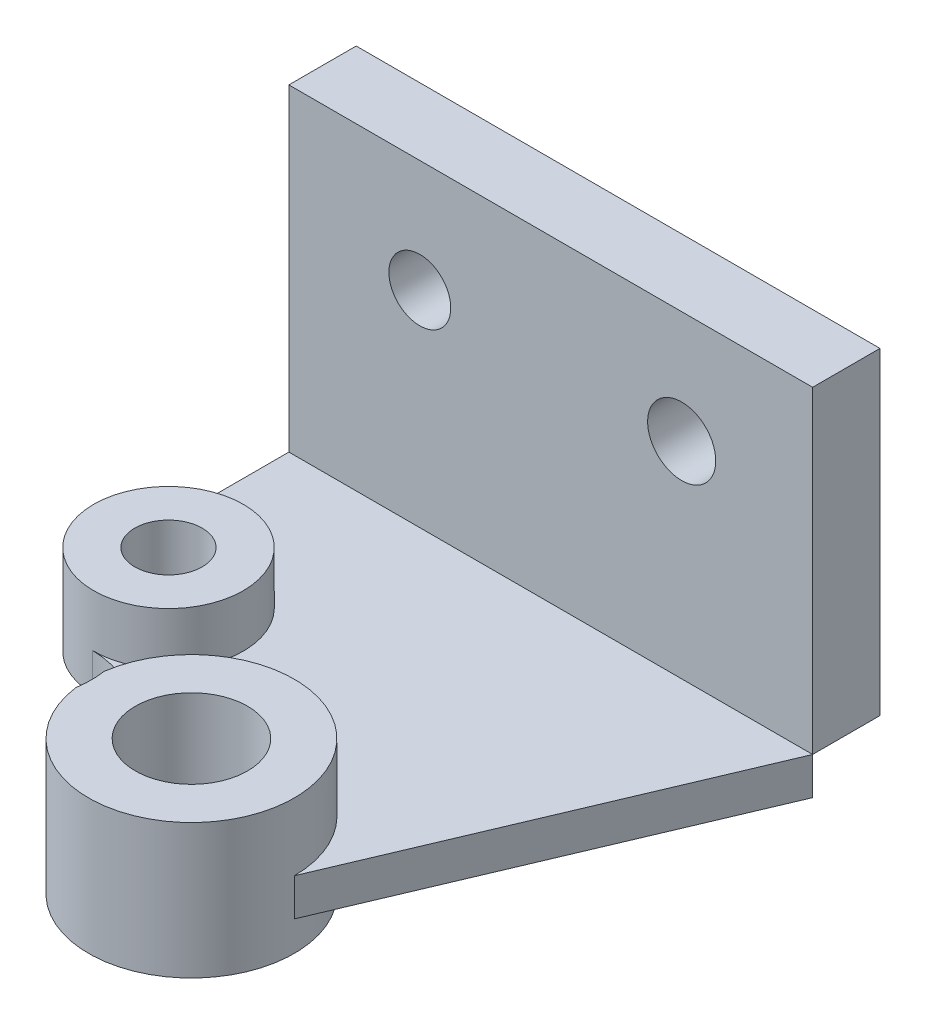
SolidWorks part; units mm, degrees
ref_plane "Front Plane" through (0, 0, 0) normal (0, 0, 1) x (1, 0, 0)
ref_plane "Top Plane" through (0, 0, 0) normal (0, 1, 0) x (1, 0, 0)
ref_plane "Right Plane" through (0, 0, 0) normal (1, 0, 0) x (0, 0, -1)
sketch "Sketch1" plane through (0, 0, 0) normal (0, 0, 1) x (1, 0, 0)
  line L1 (0, 0) -> (140, 0)
  line L2 (0, 0) -> (0, 85)
  line L3 (0, 85) -> (140, 85)
  line L4 (140, 0) -> (140, 85)
  dimension "D1" = 140
  dimension "D2" = 85
extrude "Boss-Extrude1" add sketch "Sketch1" along normal blind 18
ref_plane "Plane1" through (0, 0, 18) normal (1, 0, 0) x (0, 0, -1)
sketch "Sketch6" plane through (0, 0, 0) normal (0, -1, 0) x (1, 0, 0)
  line L0 (20, 70.7507) -> (20, 32.1792) construction
  line L1 (90, 17.1013) -> (90, 53.3456) construction
  line L2 (0, -20.5) -> (0, 56.5) construction
  line L3 (98.7977, 115.3368) -> (140, 18)
  line L5 (0, 18) -> (140, 18) construction
  line L6 (0, 70.1792) -> (0, 18)
  circle A0 centre (71.2977, 115.3368) radius 27.5
  circle A1 centre (71.2977, 115.3368) radius 15
  circle A2 centre (20, 70.1792) radius 20
  circle A3 centre (20, 70.1792) radius 9
  arc A4 (44.0507, 119.0583) -> (19.713, 90.1771) centre (19.3542, 115.1745) cw
  line M4 (140, 18) -> (0, 18)
  dimension "D2" = 30
  dimension "D3" = 55
  dimension "D6" = 18
  dimension "D7" = 40
  dimension "D8" = 25
  dimension "D1" = 50
  dimension "D4" = 100
  dimension "D5" = 38
  dimension "D9" = 20
extrude "Boss-Extrude6" add sketch "Sketch6" along normal blind 10 contours A0 A4 A2 L6 L3 M4 | A0 A4 A1 | A2 A3 region at (73.1934, 0, 88.6802) region at (70.3981, 0, 52.0183) region at (33.6432, 0, 84.0195)
extrude "Boss-Extrude7" add sketch "Sketch6<4>" along normal mid plane 36 contours A0 A4 A1 region at (73.1934, 0, 88.6802)
sketch "Sketch6<4>" plane through (0, 0, 0) normal (0, -1, 0) x (1, 0, 0) same geometry as "Sketch6"
extrude "Boss-Extrude8" add sketch "Sketch6<5>" against normal blind 14 contours A2 A3 region at (33.6432, 0, 84.0195)
sketch "Sketch6<5>" plane through (0, 0, 0) normal (0, -1, 0) x (1, 0, 0) same geometry as "Sketch6"
sketch "Sketch13" plane through (0, 0, 18) normal (0, 0, 1) x (1, 0, 0)
  line L0 (0, 85) -> (0, 0) construction
  line L1 (140, 0) -> (140, 85) construction
  line L2 (140, 85) -> (0, 85) construction
  circle A0 centre (35, 55) radius 8.2707
  circle A1 centre (105, 55) radius 9.0989
  dimension "D1" = 70
  dimension "D2" = 35
  dimension "D3" = 35
  dimension "D4" = 30
extrude "Cut-Extrude1" cut sketch "Sketch13" against normal blind 18 contours A0 | A1
